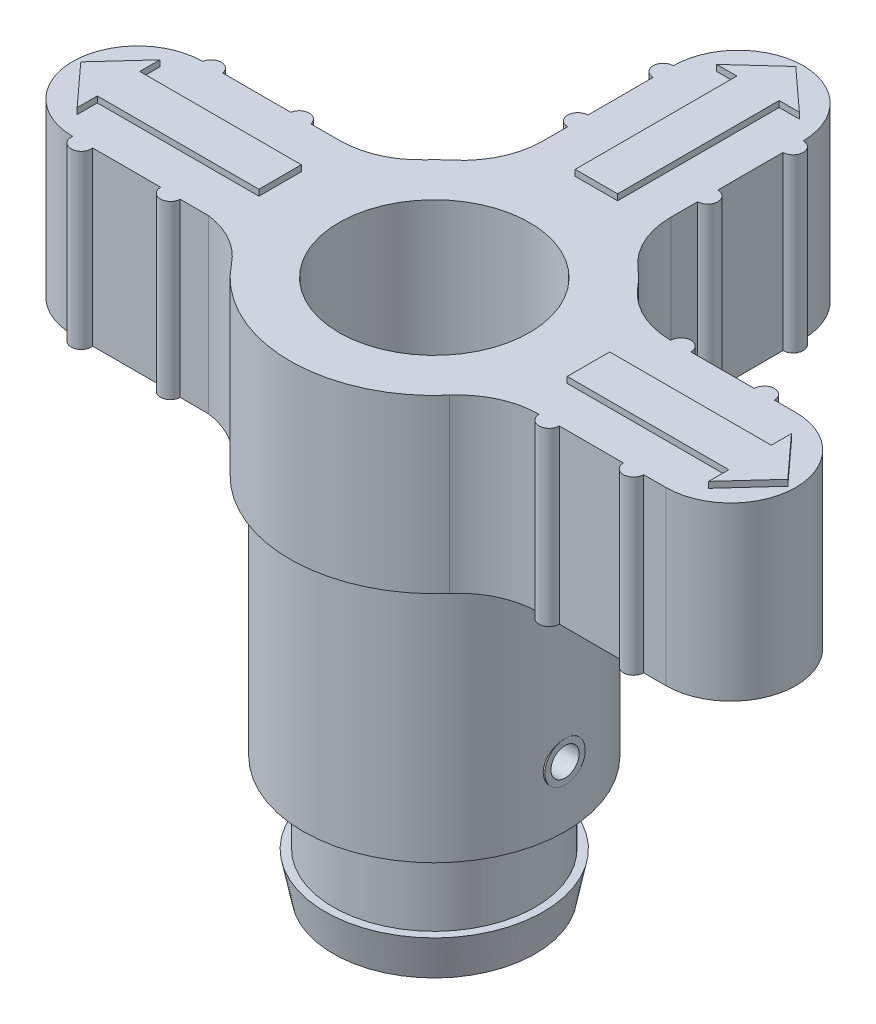
SolidWorks part; units mm, degrees
ref_plane "Front Plane" through (0, 0, 0) normal (0, 0, 1) x (1, 0, 0)
ref_plane "Top Plane" through (0, 0, 0) normal (0, 1, 0) x (1, 0, 0)
ref_plane "Right Plane" through (0, 0, 0) normal (1, 0, 0) x (0, 0, -1)
sketch "Sketch1" plane through (0, 0, 0) normal (0, 1, 0) x (1, 0, 0)
  line L0 (-1.5831, 4.2711) -> (-1.5831, 4.8861)
  line L1 (1.6336, 4.2282) -> (1.6336, 4.8861)
  line L2 (-1.5964, 7.5011) -> (-1.5831, 7.5011) construction
  line L3 (4.7711, 1.5831) -> (6.338, 1.5831)
  line L4 (4.7282, -1.6336) -> (6.3166, -1.6336)
  line L7 (-5.3215, -1.4496) -> (-7.0065, -1.4496)
  line L8 (-4.1097, 1.767) -> (-4.8251, 1.767)
  line L9 (-1.767, -3.18) -> (-1.767, -8.7259) [skipped]
  line L10 (1.4496, -3.2054) -> (1.4496, -8.7259) [skipped]
  line L11 (-5.3196, 1.767) -> (-7.0065, 1.767)
  line L12 (-1.5831, 5.3861) -> (-1.5831, 7.0011)
  line L13 (1.6336, 5.3861) -> (1.6336, 7.0011)
  line L14 (6.838, 1.5831) -> (7.3676, 1.5831)
  line L15 (6.8166, -1.6336) -> (7.3676, -1.6336)
  line L16 (-4.1246, -1.4659) -> (-4.8251, -1.4659)
  arc A0 (-2.2977, 2.7389) -> (-2.6354, 2.4156) centre (0, 0) ccw
  circle A1 centre (0, 0) radius 2.36
  arc A2 (-1.5831, 7.5011) -> (1.6336, 7.5011) centre (0.0252, 7.5011) cw
  arc A3 (7.3676, 1.5831) -> (7.3676, -1.6336) centre (7.3676, -0.0252) cw
  arc A4 (-2.8084, -2.2121) -> (2.7114, -2.33) centre (0, 0) ccw
  arc A5 (-7.5011, -1.4496) -> (-7.5011, 1.767) centre (-7.5011, 0.1587) cw
  arc A6 (1.4496, -7.3676) -> (-1.767, -7.3676) centre (-0.1587, -7.3676) cw [skipped]
  arc A7 (2.7389, 2.2977) -> (2.33, 2.7114) centre (0, 0) ccw
  arc A8 (4.2282, -1.6336) -> (2.7114, -2.33) centre (4.2282, -3.6336) ccw
  arc A9 (-4.1246, -1.4659) -> (-2.8084, -2.2121) centre (-4.3796, -3.4496) cw
  arc A10 (4.2711, 1.5831) -> (2.7389, 2.2977) centre (4.2711, 3.5831) cw
  arc A11 (-4.1097, 1.767) -> (-2.6354, 2.4156) centre (-4.1097, 3.767) ccw
  arc A12 (1.6336, 4.2282) -> (2.33, 2.7114) centre (3.6336, 4.2282) ccw
  arc A13 (-1.5831, 4.2711) -> (-2.2977, 2.7389) centre (-3.5831, 4.2711) cw
  arc A14 (-7.5011, 1.767) -> (-7.0065, 1.767) centre (-7.2538, 1.7303) cw
  arc A15 (-5.3196, 1.767) -> (-4.8251, 1.767) centre (-5.0723, 1.7298) cw
  arc A17 (-7.5011, -1.4496) -> (-7.0065, -1.4496) centre (-7.2538, -1.4864) ccw
  arc A18 (-1.5831, 7.5011) -> (-1.5831, 7.0011) centre (-1.5831, 7.2511) ccw
  arc A19 (-1.5831, 5.3861) -> (-1.5831, 4.8861) centre (-1.5831, 5.1361) ccw
  arc A20 (1.6336, 7.5011) -> (1.6336, 7.0011) centre (1.6336, 7.2511) cw
  arc A21 (1.6336, 5.3861) -> (1.6336, 4.8861) centre (1.6336, 5.1361) cw
  arc A22 (4.2711, 1.5831) -> (4.7711, 1.5831) centre (4.5211, 1.5831) cw
  arc A23 (6.338, 1.5831) -> (6.838, 1.5831) centre (6.588, 1.5831) cw
  arc A24 (4.2282, -1.6336) -> (4.7282, -1.6336) centre (4.4782, -1.6336) ccw
  arc A25 (6.3166, -1.6336) -> (6.8166, -1.6336) centre (6.5666, -1.6336) ccw
  arc A26 (-5.3215, -1.4496) -> (-4.8251, -1.4659) centre (-5.0733, -1.4578) ccw
  point P29 (-0.0667, 0.0667)
  point P69 (3.1799, -1.6336)
  point P72 (-3.2679, -1.4496)
  point P75 (3.2054, 1.5831)
  dimension "D2" = 4.72
  dimension "D3" = 0.25
  dimension "D11" = 0.2483
  dimension "D6" = 1.6083
  dimension "D1" = 3.23
  dimension "D18" = 6.5666
  dimension "D19" = 6.588
  dimension "D7" = 0.0252
  dimension "D8" = 2.7114
  dimension "D9" = 7.3676
  dimension "D12" = 4.1246
  dimension "D13" = 4.8251
  dimension "D14" = 5.0723
  dimension "D15" = 5.0733
  dimension "D16" = 5.1361
  dimension "D17" = 3.18
  dimension "D20" = 3.2054
  dimension "D21" = 8.7259
  dimension "D22" = 7.0065
  dimension "D4" = 4
extrude "Boss-Extrude3" add sketch "Sketch1" along normal blind 4.25
sketch "Sketch3" plane through (0, 4.25, 0) normal (0, 1, 0) x (1, 0, 0)
  line L0 (-8.8502, 0.0984) -> (-7.9154, 1.1236)
  line L1 (-7.9154, 1.1236) -> (-7.9154, 0.6236)
  line L2 (-8.8502, 0.0984) -> (-7.9154, -0.9268)
  line L3 (-7.9154, -0.9268) -> (-7.9154, -0.4268)
  line L4 (-7.9154, 0.6236) -> (-3.9154, 0.6236)
  line L5 (-7.9154, -0.4268) -> (-3.9154, -0.4268)
  line L6 (-3.9154, 0.6236) -> (-3.9154, -0.4268)
  line L7 (0.6236, 7.9154) -> (0.6236, 3.9154)
  line L8 (-0.4268, 7.9154) -> (-0.4268, 3.9154)
  line L9 (-0.9268, 7.9154) -> (-0.4268, 7.9154)
  line L10 (1.1236, 7.9154) -> (0.6236, 7.9154)
  line L11 (0.0984, 8.8502) -> (1.1236, 7.9154)
  line L12 (0.0984, 8.8502) -> (-0.9268, 7.9154)
  line L13 (7.9154, -0.6236) -> (3.9154, -0.6236)
  line L14 (7.9154, 0.4268) -> (3.9154, 0.4268)
  line L15 (7.9154, 0.9268) -> (7.9154, 0.4268)
  line L16 (7.9154, -1.1236) -> (7.9154, -0.6236)
  line L17 (8.8502, -0.0984) -> (7.9154, -1.1236)
  line L18 (8.8502, -0.0984) -> (7.9154, 0.9268)
  line L19 (-1.5831, 7.0011) -> (-1.5831, 5.3861) construction
  line L25 (-0.4268, 3.9154) -> (0.6236, 3.9154)
  line L26 (3.9154, 0.4268) -> (3.9154, -0.6236)
  line L28 (-0.6236, -7.9154) -> (-0.6236, -3.9154) [skipped]
  line L29 (0.4268, -7.9154) -> (0.4268, -3.9154) [skipped]
  line L30 (-0.0984, -8.8502) -> (0.9268, -7.9154) [skipped]
  line L31 (-0.0984, -8.8502) -> (-1.1236, -7.9154) [skipped]
  line L32 (-1.1236, -7.9154) -> (-0.6236, -7.9154) [skipped]
  line L33 (0.9268, -7.9154) -> (0.4268, -7.9154) [skipped]
  point P32 (0, 0)
  dimension "D1" = 0.5
  dimension "D2" = 0.5
  dimension "D3" = 4
  dimension "D5" = 0.4595
  dimension "D6" = 0.6563
  dimension "D7" = 1.4847
  dimension "D8" = 1.5831
  dimension "D9" = 5.4984
  dimension "D10" = 10.4332
  dimension "D11" = 0.51
  dimension "D4" = 4
extrude "Boss-Extrude4" add sketch "Sketch3" along normal blind 0.15 contours L25 L7 L10 L11 L12 L9 L8 | L6 L5 L3 L2 L0 L1 L4 | L26 L13 L16 L17 L18 L15 L14
sketch "Sketch6" plane through (0, 0, 0) normal (0, -1, 0) x (-1, 0, 0)
  circle A0 centre (0, 0) radius 3.25
  dimension "D1" = 6.5
extrude "Boss-Extrude5" add sketch "Sketch6" along normal blind 6 separate body
ref_plane "Plane1" through (3.25, 0, 0) normal (1, 0, 0) x (0, 0, -1)
sketch "Sketch10" plane through (3.25, 0, 0) normal (1, 0, 0) x (0, 0, -1)
  line L0 (-0.0126, -6) -> (-0.0126, -5) construction
  line L1 (-3.25, -6) -> (3.25, -6) construction
  circle A0 centre (-0.0126, -4.5) radius 0.5
  dimension "D2" = 1
ref_plane "Plane2" through (-3.25, 0, 0) normal (-1, 0, 0) x (0, 0, 1)
sketch "Sketch14" plane through (0, -6, 0) normal (0, -1, 0) x (1, 0, 0)
  circle A0 centre (0, 0) radius 2.36
  dimension "D1" = 4.72
ref_plane "Plane3" through (0, 0, -3.25) normal (0, 0, -1) x (-1, 0, 0)
ref_plane "Plane4" through (0, 0, 3.25) normal (0, 0, 1) x (1, 0, 0)
sketch "Sketch17" plane through (0.1088, 0.2623, -3.25) normal (0, 0, -1) x (-1, 0, 0)
  line L0 (0.3125, -5.2833) -> (0.1088, -6.2623) construction
  line L1 (-2.2512, -6.2623) -> (2.4688, -6.2623) construction
  circle A0 centre (0.3125, -4.7833) radius 0.5
  dimension "D2" = 1
ref_plane "Plane6" through (0, -6, 0) normal (0, -1, 0) x (-1, 0, 0)
sketch "Sketch38" plane through (0, -6, 0) normal (0, -1, 0) x (1, 0, 0)
  circle A0 centre (0, 0) radius 2
  dimension "D1" = 4
extrude "Cut-Extrude22" cut sketch "Sketch38" against normal through all
sketch "Sketch23" plane through (0, -6, 0) normal (0, -1, 0) x (-1, 0, 0)
  circle A0 centre (0, 0) radius 2.5
  dimension "D1" = 5
extrude "Boss-Extrude7" add sketch "Sketch23" along normal blind 2 separate body
ref_plane "Plane8" through (0, -9, 0) normal (0, -1, 0) x (-1, 0, 0)
sketch "Sketch25" plane through (0, -9, 0) normal (0, -1, 0) x (-1, 0, 0)
  circle A0 centre (0, 0) radius 2.5
  dimension "D1" = 5
ref_plane "Plane9" through (0, -8, 0) normal (0, -1, 0) x (-1, 0, 0)
sketch "Sketch36" plane through (0, -8, 0) normal (0, -1, 0) x (-1, 0, 0)
  circle A0 centre (0, 0) radius 2.7
  dimension "D1" = 5.4
loft "Loft3" add profiles "Sketch25", "Sketch36" connector at (-1.1013, -9, -2.2444) connector at (-1.3037, -8, -2.3644)
extrude "Cut-Extrude21" cut sketch "Sketch14" against normal mid plane 5 contours A0
extrude "Cut-Extrude12" cut sketch "Sketch10" against normal blind 2
sketch "Sketch28" plane through (0, -6, 0) normal (0, -1, 0) x (-1, 0, 0)
  circle A0 centre (0, 0) radius 2.36
  dimension "D1" = 4.72
extrude "Boss-Extrude11" add sketch "Sketch17" against normal blind 3
extrude "Boss-Extrude12" add sketch "Sketch10<7>" against normal blind 6.5
sketch "Sketch10<7>" plane through (3.25, 0, 0) normal (1, 0, 0) x (0, 0, -1) same geometry as "Sketch10"
sketch "Sketch32" plane through (3.25, 0, 0) normal (1, 0, 0) x (0, 0, -1)
  circle A0 centre (-0.0126, -4.5) radius 0.5
  circle A1 centre (-0.0126, -4.5) radius 0.3489
  dimension "D1" = 0.6978
extrude "Cut-Extrude18" cut sketch "Sketch32" against normal through all contours A1
sketch "Sketch34" plane through (0, 0, -3.25) normal (0, 0, -1) x (-1, 0, 0)
  circle A0 centre (0.2037, -4.521) radius 0.35
  dimension "D1" = 0.7
extrude "Cut-Extrude20" cut sketch "Sketch34" against normal blind 3
ref_plane "Plane10" through (0, -1, 0) normal (0, -1, 0) x (-1, 0, 0)
sketch "Sketch39" plane through (0, -9, 0) normal (0, -1, 0) x (1, 0, 0)
  circle A0 centre (0, 0) radius 2.36
  dimension "D1" = 4.72
extrude "Cut-Extrude24" cut sketch "Sketch39" against normal mid plane 8
sketch "Sketch37" plane through (0, -1, 0) normal (0, -1, 0) x (-1, 0, 0)
  circle A0 centre (0, 0) radius 2.36 construction
  circle A1 centre (0, 0) radius 2.36
extrude "Boss-Extrude13" add sketch "Sketch37" along normal blind 1
equation "\"Blue_CircleTopOuter\"= 7.15"
equation "\"Branch _Width\"= 3.23"
equation "\"Arrow_Length\"= 3.00"
equation "\"Blue_CircleInner\"= 4.72"
equation "\"Branch_Height\"= 4.25"
equation "\"D2@Sketch1\"= \"Blue_CircleInner\""
equation "\"Arrow_Height\"= 0.35"
equation "\"D1@Boss-Extrude3\"=\"Branch_Height\""
equation "\"D1@Sketch14\"=\"Blue_CircleInner\""
equation "\"D1@Sketch39\"=\"Blue_CircleInner\""
